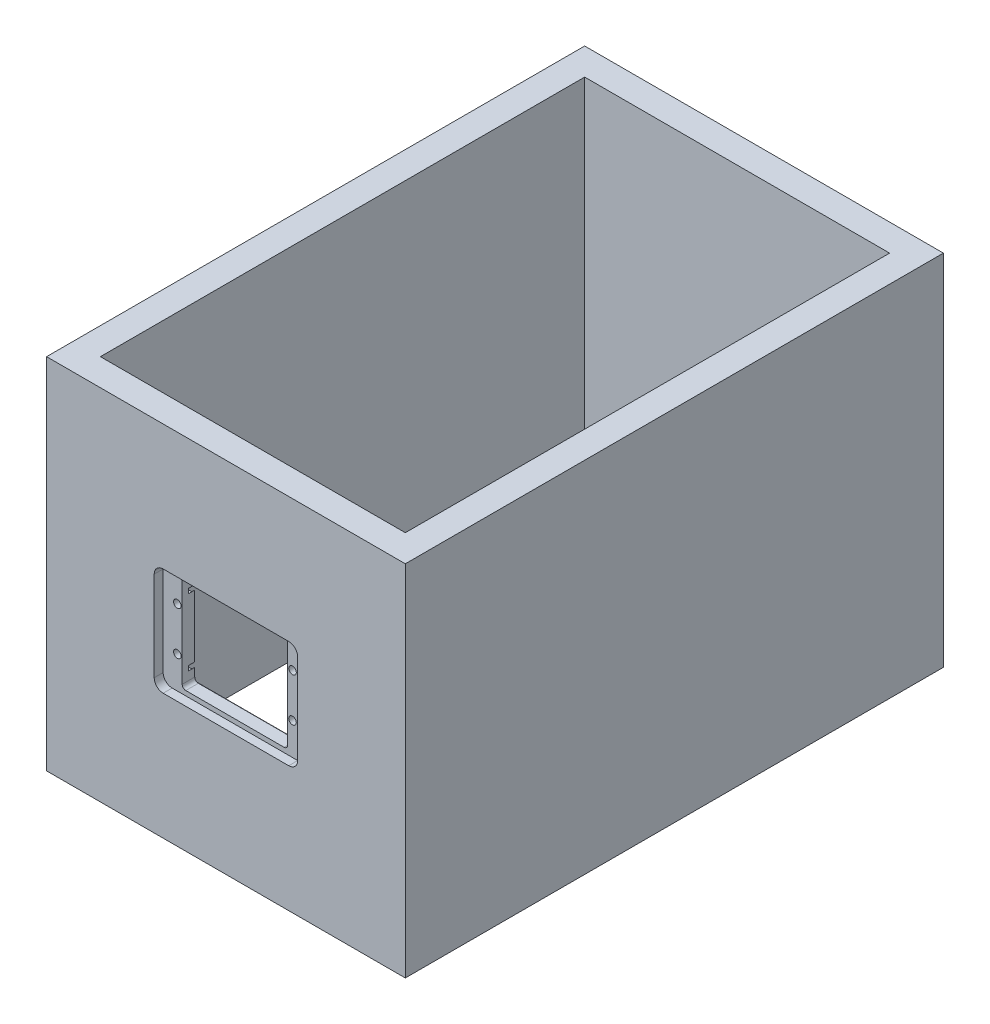
SolidWorks part; units mm, degrees
ref_plane "前基準面" through (0, 0, 0) normal (0, 0, 1) x (1, 0, 0)
ref_plane "上基準面" through (0, 0, 0) normal (0, 1, 0) x (1, 0, 0)
ref_plane "右基準面" through (0, 0, 0) normal (1, 0, 0) x (0, 0, -1)
sketch "草圖1" plane through (0, 0, 0) normal (0, 0, 1) x (1, 0, 0)
  line L1 (-100, 100) -> (100, 100)
  line L2 (-100, 100) -> (-100, -100)
  line L3 (-100, -100) -> (100, -100)
  line L4 (100, 100) -> (100, -100)
  line L5 (-100, 100) -> (100, -100) construction
  line L6 (-100, -100) -> (100, 100) construction
  point P0 (0, 0)
  dimension "D1" = 200
  dimension "D2" = 200
extrude "填料-伸長1" add sketch "草圖1" along normal blind 300
sketch "草圖2" plane through (0, -100, 0) normal (0, -1, 0) x (1, 0, 0)
  line L0 (-100, 0) -> (100, 0) construction
  line L1 (-85, 285) -> (85, 285)
  line L2 (-85, 285) -> (-85, 15)
  line L3 (-85, 15) -> (85, 15)
  line L4 (85, 285) -> (85, 15)
  line L5 (-85, 285) -> (85, 15) construction
  line L6 (-85, 15) -> (85, 285) construction
  line L7 (-100, 300) -> (100, 300) construction
  line L8 (-100, 300) -> (-100, 0) construction
  line L9 (100, 300) -> (100, 0) construction
  point P0 (0, 150)
  dimension "D1" = 15
  dimension "D2" = 15
  dimension "D3" = 15
  dimension "D4" = 15
extrude "除料-伸長1" cut sketch "草圖2" against normal through all
sketch "草圖3" plane through (0, 0, 0) normal (0, 0, -1) x (-1, 0, 0)
  circle A0 centre (0, 0) radius 7.5
  dimension "D1" = 15
extrude "除料-伸長2" cut sketch "草圖3" against normal up to next
sketch "草圖4" plane through (0, 0, 285) normal (0, 0, -1) x (-1, 0, 0)
  line L0 (0, 26.9) -> (0, -26.9) construction
  line L1 (-34.9, 26.9) -> (34.9, 26.9) construction
  line L2 (-34.9, 26.9) -> (-34.9, -26.9) construction
  line L3 (-34.9, -26.9) -> (34.9, -26.9) construction
  line L4 (34.9, 26.9) -> (34.9, -26.9) construction
  line L5 (-34.9, 26.9) -> (34.9, -26.9) construction
  line L6 (-34.9, -26.9) -> (34.9, 26.9) construction
  line L7 (34.9, 0) -> (-34.9, 0) construction
  line L8 (27.4, 27.4) -> (-27.4, 27.4)
  line L9 (29.4, 25.4) -> (29.4, -25.4)
  line L10 (27.4, -27.4) -> (-27.4, -27.4)
  line L11 (-29.4, 25.4) -> (-29.4, -25.4)
  line L12 (29.4, 27.4) -> (-29.4, -27.4) construction
  line L13 (29.4, -27.4) -> (-29.4, 27.4) construction
  circle A0 centre (21.9, 19.4) radius 4 construction
  circle A1 centre (-21.9, 19.4) radius 4 construction
  circle A2 centre (21.9, -19.4) radius 4 construction
  arc A3 (29.4, -25.4) -> (27.4, -27.4) centre (27.4, -25.4) cw
  arc A4 (-27.4, -27.4) -> (-29.4, -25.4) centre (-27.4, -25.4) cw
  arc A5 (-27.4, 27.4) -> (-29.4, 25.4) centre (-27.4, 25.4) ccw
  arc A6 (27.4, 27.4) -> (29.4, 25.4) centre (27.4, 25.4) cw
  circle A7 centre (-32.1, 12.1) radius 2.1
  circle A8 centre (32.1, 12.1) radius 2.1
  circle A9 centre (32.1, -12.1) radius 2.1
  circle A10 centre (-32.1, -12.1) radius 2.1
  point P0 (0, 0)
  point P12 (0, 0)
  dimension "D3" = 8
  dimension "D8" = 2
  dimension "D11" = 4.2
  dimension "D1" = 69.8
  dimension "D2" = 53.8
  dimension "D4" = 13
  dimension "D5" = 7.5
  dimension "D6" = 8
  dimension "D7" = 7.5
  dimension "D9" = 2.8
  dimension "D10" = 14.8
  dimension "D12" = 58.8
  dimension "D13" = 54.8
extrude "除料-伸長3" cut sketch "草圖4" against normal up to next
sketch "草圖5" plane through (0, 0, 300) normal (0, 0, 1) x (1, 0, 0)
  line L1 (-35, 30) -> (35, 30)
  line L2 (-40, 25) -> (-40, -25)
  line L3 (-35, -30) -> (35, -30)
  line L4 (40, 25) -> (40, -25)
  line L5 (-40, 30) -> (40, -30) construction
  line L6 (-40, -30) -> (40, 30) construction
  arc A0 (-40, -25) -> (-35, -30) centre (-35, -25) ccw
  arc A1 (35, -30) -> (40, -25) centre (35, -25) ccw
  arc A2 (35, 30) -> (40, 25) centre (35, 25) cw
  arc A3 (-35, 30) -> (-40, 25) centre (-35, 25) ccw
  point P0 (0, 0)
  dimension "D3" = 5
  dimension "D1" = 80
  dimension "D2" = 60
extrude "除料-伸長4" cut sketch "草圖5" against normal blind 5
sketch "草圖6" plane through (0, 0, 285) normal (0, 0, -1) x (-1, 0, 0)
  line L1 (-33.25, 30.25) -> (33.25, 30.25)
  line L2 (-38.25, 25.25) -> (-38.25, -25.25)
  line L3 (-33.25, -30.25) -> (33.25, -30.25)
  line L4 (38.25, 25.25) -> (38.25, -25.25)
  line L5 (-38.25, 30.25) -> (38.25, -30.25) construction
  line L6 (-38.25, -30.25) -> (38.25, 30.25) construction
  arc A0 (-38.25, -25.25) -> (-33.25, -30.25) centre (-33.25, -25.25) ccw
  arc A1 (33.25, -30.25) -> (38.25, -25.25) centre (33.25, -25.25) ccw
  arc A2 (33.25, 30.25) -> (38.25, 25.25) centre (33.25, 25.25) cw
  arc A3 (-33.25, 30.25) -> (-38.25, 25.25) centre (-33.25, 25.25) ccw
  point P0 (0, 0)
  dimension "D3" = 5
  dimension "D1" = 76.5
  dimension "D2" = 60.5
extrude "除料-伸長5" cut sketch "草圖6" against normal blind 3
sketch "草圖7" plane through (0, 0, 288) normal (0, 0, -1) x (-1, 0, 0)
  line L0 (38.25, -25.25) -> (38.25, 25.25) construction
  line L1 (-33.25, -30.25) -> (33.25, -30.25) construction
  line L2 (-38.25, 25.25) -> (-38.25, -25.25) construction
  line L3 (33.25, 30.25) -> (-33.25, 30.25) construction
  line L4 (38.25, -25.25) -> (38.25, 25.25) construction
  line L5 (-33.25, -30.25) -> (33.25, -30.25) construction
  line L6 (-38.25, 25.25) -> (-38.25, -25.25) construction
  line L7 (33.25, 30.25) -> (-33.25, 30.25) construction
  line L8 (0, 42.4952) -> (0, -47.2533) construction
  line L9 (-57.5161, 0) -> (70.029, 0) construction
  arc A0 (38.25, 25.25) -> (33.25, 30.25) centre (33.25, 25.25) ccw construction
  arc A1 (33.25, -30.25) -> (38.25, -25.25) centre (33.25, -25.25) ccw construction
  arc A2 (-38.25, -25.25) -> (-33.25, -30.25) centre (-33.25, -25.25) ccw construction
  arc A3 (-33.25, 30.25) -> (-38.25, 25.25) centre (-33.25, 25.25) ccw construction
  circle A4 centre (32.1, -12.1) radius 2.1 construction
  circle A5 centre (32.1, 12.1) radius 2.1 construction
  circle A6 centre (-32.1, -12.1) radius 2.1 construction
  circle A7 centre (-32.1, 12.1) radius 2.1 construction
  arc A8 (38.25, 25.25) -> (33.25, 30.25) centre (33.25, 25.25) ccw construction
  arc A9 (33.25, -30.25) -> (38.25, -25.25) centre (33.25, -25.25) ccw construction
  arc A10 (-38.25, -25.25) -> (-33.25, -30.25) centre (-33.25, -25.25) ccw construction
  arc A11 (-33.25, 30.25) -> (-38.25, 25.25) centre (-33.25, 25.25) ccw construction
  circle A12 centre (32.1, -12.1) radius 2.1 construction
  circle A13 centre (32.1, 12.1) radius 2.1 construction
  circle A14 centre (-32.1, -12.1) radius 2.1 construction
  circle A15 centre (-32.1, 12.1) radius 2.1 construction
  circle A16 centre (-32.1, 19.4) radius 3
  circle A17 centre (-32.1, -19.4) radius 3
  circle A18 centre (32.1, 17.9) radius 3
  circle A19 centre (32.1, -19.4) radius 3
  line M25 (-29.4, -25.4) -> (-29.4, 25.4)
  line M29 (29.4, 25.4) -> (29.4, -25.4)
  dimension "D1" = 6
  dimension "D4" = 6
  dimension "D2" = 7.3
  dimension "D3" = 5.8
extrude "除料-伸長6" cut sketch "草圖7" against normal blind 3.5 contours A16 M25 | A19 M29 | A17 | A18 region at (32.1537, 19.4, 288) region at (-32.1537, -19.4, 288)
